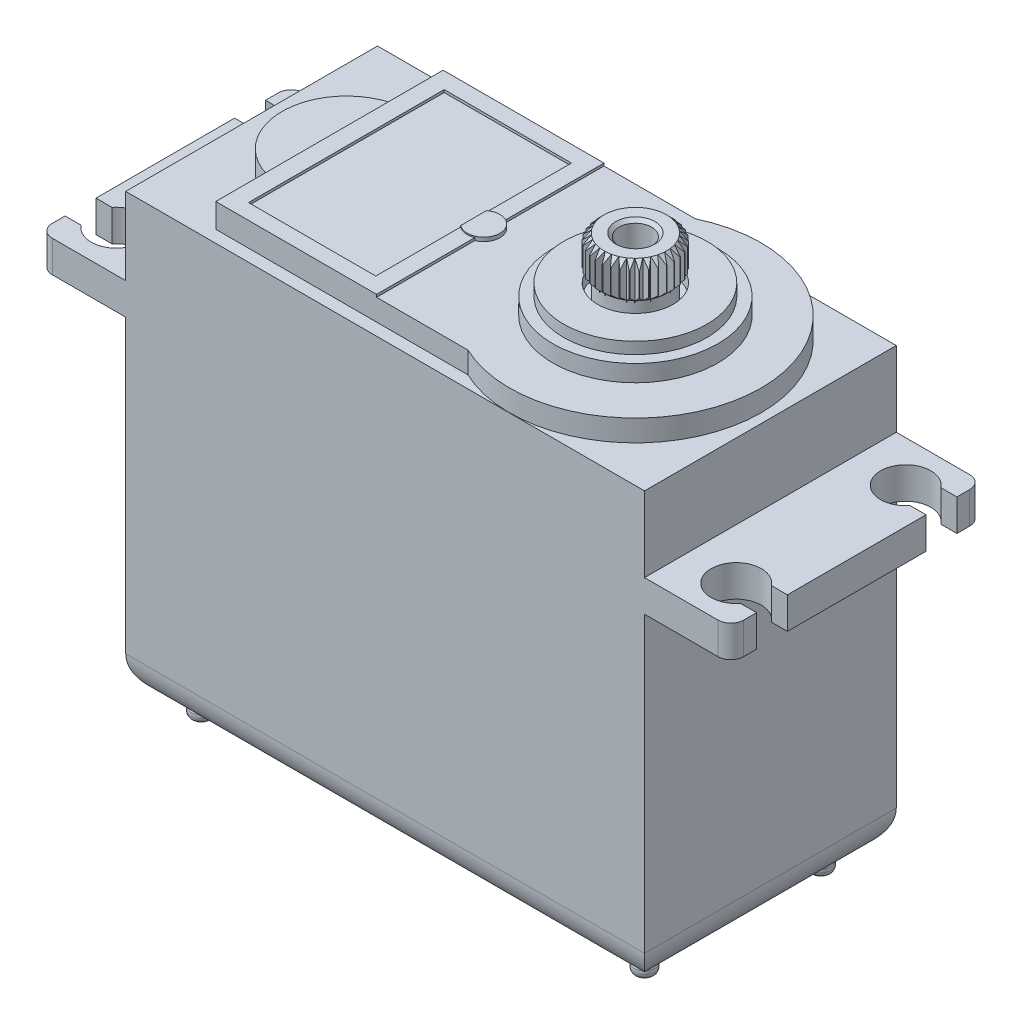
SolidWorks part; units mm, degrees
ref_plane "Front Plane" through (0, 0, 0) normal (0, 0, 1) x (1, 0, 0)
ref_plane "Top Plane" through (0, 0, 0) normal (0, 1, 0) x (1, 0, 0)
ref_plane "Right Plane" through (0, 0, 0) normal (1, 0, 0) x (0, 0, -1)
sketch "Sketch1" plane through (0, 0, 0) normal (0, 1, 0) x (1, 0, 0)
  line L1 (-18.6567, 11.3793) -> (21.6633, 11.3793)
  line L2 (-18.6567, 11.3793) -> (-18.6567, -8.1907)
  line L3 (-18.6567, -8.1907) -> (21.6633, -8.1907)
  line L4 (21.6633, 11.3793) -> (21.6633, -8.1907)
extrude "Boss-Extrude1" add sketch "Sketch1" along normal blind 35.37
sketch "Sketch2" plane through (21.6633, 0, 0) normal (1, 0, 0) x (0, 0, -1)
  line L0 (-8.1907, 0) -> (-8.1907, 3)
  line L1 (-8.1907, 35.37) -> (-8.1907, 0) construction
  line L2 (-8.1907, 3) -> (-5.1907, 0)
  line L3 (-8.1907, 0) -> (11.3793, 0) construction
  line L4 (-5.1907, 0) -> (-8.1907, 0)
  line L5 (1.5943, 0) -> (1.5943, 35.37) construction
  line L6 (-8.1907, 35.37) -> (11.3793, 35.37) construction
  line L7 (8.3793, 0) -> (11.3793, 0)
  line L8 (11.3793, 3) -> (8.3793, 0)
  line L9 (11.3793, 0) -> (11.3793, 3)
extrude "Cut-Extrude1" cut sketch "Sketch2" against normal up to next
sketch "Sketch3" plane through (0, 0, 8.1907) normal (0, 0, 1) x (1, 0, 0)
  line L0 (21.6633, 0) -> (18.6633, 0)
  line L1 (-18.6567, 0) -> (21.6633, 0) construction
  line L2 (18.6633, 0) -> (21.6633, 3)
  line L3 (21.6633, 35.37) -> (21.6633, 3) construction
  line L4 (21.6633, 3) -> (21.6633, 0)
  line L5 (1.5033, 35.37) -> (1.5033, 0) construction
  line L6 (-18.6567, 35.37) -> (21.6633, 35.37) construction
  line L7 (-18.6567, 3) -> (-18.6567, 0)
  line L8 (-15.6567, 0) -> (-18.6567, 3)
  line L9 (-18.6567, 0) -> (-15.6567, 0)
extrude "Cut-Extrude2" cut sketch "Sketch3" against normal up to next
fillet "Fillet2" radius 3 4 edges at (21.6633, 3, -1.5943) (1.5033, 3, 8.1907) (-18.6567, 3, -1.5943) (1.5033, 3, -11.3793)
sketch "Sketch5" plane through (21.6633, 0, 0) normal (1, 0, 0) x (0, 0, -1)
  line L0 (1.5943, 35.37) -> (1.5943, 29.53) construction
  line L1 (-8.1907, 35.37) -> (11.3793, 35.37) construction
  line L2 (-8.1907, 29.53) -> (1.5943, 29.53)
  line L3 (-8.1907, 35.37) -> (-8.1907, 4.2426) construction
  line L4 (1.5943, 29.53) -> (11.3793, 29.53)
  line L5 (11.3793, 35.37) -> (11.3793, 4.2426) construction
  line L6 (11.3793, 29.53) -> (11.3793, 27.07)
  line L7 (11.3793, 27.07) -> (-8.1907, 27.07)
  line L8 (-8.1907, 27.07) -> (-8.1907, 29.53)
extrude "Boss-Extrude2" add sketch "Sketch5" along normal blind 6.71
sketch "Sketch7" plane through (-18.6567, 0, 0) normal (-1, 0, 0) x (0, 0, 1)
  line L0 (-1.5943, 35.37) -> (-1.5943, 29.3613) construction
  line L1 (-11.3793, 29.3613) -> (-1.5943, 29.3613)
  line L2 (-1.5943, 29.3613) -> (8.1907, 29.3613)
  line L3 (8.1907, 29.3613) -> (8.1907, 26.9013)
  line L4 (8.1907, 26.9013) -> (-11.3793, 26.9013)
  line L5 (-11.3793, 26.9013) -> (-11.3793, 29.3613)
  line L6 (-11.3793, 35.37) -> (8.1907, 35.37) construction
  line L7 (8.1907, 35.37) -> (8.1907, 4.2426) construction
  line L8 (-11.3793, 35.37) -> (-11.3793, 4.2426) construction
extrude "Boss-Extrude3" add sketch "Sketch7" along normal blind 6.71
sketch "Sketch8" plane through (0, 29.53, 0) normal (0, 1, 0) x (1, 0, 0)
  line L0 (28.3733, 1.5943) -> (-25.3667, 1.5943) construction
  line L2 (-25.3667, -8.1907) -> (-25.3667, 11.3793) construction
  line L4 (28.3733, -3.7925) -> (27.1303, -3.7925)
  line L5 (28.3733, 11.3793) -> (28.3733, -8.1907) construction
  line L6 (28.3733, 8.181) -> (28.3733, 9.381)
  line L7 (28.3733, 9.381) -> (27.1303, 9.381)
  line L8 (28.3733, 8.181) -> (28.3733, 6.981)
  line L9 (28.3733, 6.981) -> (27.1303, 6.981)
  line L10 (28.3733, -4.9925) -> (28.3733, -3.7925)
  line L11 (28.3733, -6.1925) -> (27.1303, -6.1925)
  line L12 (28.3733, -4.9925) -> (28.3733, -6.1925)
  line L13 (1.5033, 11.3793) -> (1.5033, -8.1907) construction
  line L14 (21.6633, 11.3793) -> (-18.6567, 11.3793) construction
  line L15 (-18.6567, -8.1907) -> (21.6633, -8.1907) construction
  line L24 (-25.3667, 6.981) -> (-24.1237, 6.981)
  line L25 (-25.3667, -4.9925) -> (-25.3667, -6.1925)
  line L26 (-25.3667, -6.1925) -> (-24.1237, -6.1925)
  line L27 (-25.3667, -4.9925) -> (-25.3667, -3.7925)
  line L28 (-25.3667, -3.7925) -> (-24.1237, -3.7925)
  line L29 (-25.3667, 8.181) -> (-25.3667, 6.981)
  line L30 (-25.3667, 9.381) -> (-24.1237, 9.381)
  line L31 (-25.3667, 8.181) -> (-25.3667, 9.381)
  arc A0 (27.1303, -3.7925) -> (27.1303, -6.1925) centre (25.5933, -4.9925) ccw
  arc A1 (27.1303, 6.981) -> (27.1303, 9.381) centre (25.5933, 8.181) cw
  arc A4 (-24.1237, 6.981) -> (-24.1237, 9.381) centre (-22.5867, 8.181) ccw
  arc A5 (-24.1237, -3.7925) -> (-24.1237, -6.1925) centre (-22.5867, -4.9925) cw
extrude "Cut-Extrude3" cut sketch "Sketch8" against normal up to next
sketch "Sketch9" plane through (0, 35.37, 0) normal (0, 1, 0) x (1, 0, 0)
  line L0 (6.9933, -8.1907) -> (6.9933, -7.2426) construction
  line L1 (-18.6567, 6.4311) -> (-12.6067, 6.4311) construction
  line L2 (6.9933, 11.3793) -> (6.9933, 10.4311) construction
  line L3 (-18.6567, -3.2426) -> (-12.6067, -3.2426) construction
  line L4 (-18.6567, -8.1907) -> (-18.6567, 11.3793) construction
  line L5 (-18.6567, 1.5943) -> (21.6633, 1.5943) construction
  line L6 (-12.6067, 10.4311) -> (6.9933, 10.4311)
  line L7 (-18.6567, 11.3793) -> (-18.6567, -8.1907) construction
  line L8 (-12.6067, -7.2426) -> (-12.6067, -3.2426)
  line L9 (21.6633, -8.1907) -> (21.6633, 11.3793) construction
  line L10 (-12.6067, 10.4311) -> (-12.6067, 6.4311)
  line L11 (-12.6067, -7.2426) -> (6.9933, -7.2426)
  line L12 (21.6633, 1.5943) -> (20.9438, 1.5943) construction
  line L13 (21.6633, 11.3793) -> (-18.6567, 11.3793) construction
  arc A0 (6.9933, 10.4311) -> (6.9933, -7.2426) centre (11.1697, 1.5943) cw
  arc A1 (-12.6067, 6.4311) -> (-12.6067, -3.2426) centre (-11.2767, 1.5943) ccw
extrude "Boss-Extrude4" add sketch "Sketch9" along normal blind 1.67
sketch "Sketch10" plane through (0, 37.04, 0) normal (0, 1, 0) x (1, 0, 0)
  circle A1 centre (11.1697, 1.5943) radius 6.415
extrude "Boss-Extrude5" add sketch "Sketch10" along normal blind 1.3
sketch "Sketch11" plane through (0, 38.34, 0) normal (0, 1, 0) x (-1, 0, 0)
  circle A2 centre (-11.1697, -1.5943) radius 5.575
extrude "Boss-Extrude6" add sketch "Sketch11" along normal blind 0.9
sketch "Sketch12" plane through (0, 39.24, 0) normal (0, 1, 0) x (1, 0, 0)
  circle A1 centre (11.1697, 1.5943) radius 2.925
extrude "Cut-Extrude4" cut sketch "Sketch12" against normal blind 1
sketch "Sketch13" plane through (0, 38.24, 0) normal (0, 1, 0) x (-1, 0, 0)
  circle A0 centre (-11.1697, -1.5943) radius 2.425
extrude "Boss-Extrude7" add sketch "Sketch13" along normal blind 1.5
sketch "Sketch14" plane through (0, 39.74, 0) normal (0, 1, 0) x (1, 0, 0)
  circle A0 centre (11.1697, 1.5943) radius 2.925
extrude "Boss-Extrude8" add sketch "Sketch14" along normal blind 2.86
sketch "Sketch15" plane through (0, 42.6, 0) normal (0, 1, 0) x (1, 0, 0)
  circle A0 centre (11.1697, 1.5943) radius 1.27
extrude "Cut-Extrude5" cut sketch "Sketch15" against normal blind 7
sketch "Sketch16" plane through (0, 37.04, 0) normal (0, 1, 0) x (1, 0, 0)
  line L0 (-12.6067, -7.2426) -> (6.9933, -7.2426) construction
  line L1 (-12.6067, 10.4311) -> (-0.1067, 10.4311)
  line L2 (-12.6067, 10.4311) -> (-12.6067, -7.2426)
  line L3 (-12.6067, -7.2426) -> (-0.1067, -7.2426)
  line L4 (-0.1067, 10.4311) -> (-0.1067, -7.2426)
  line L5 (-6.3168, 9.1673) -> (-6.3567, 10.4311) construction
  line L6 (-11.2628, 9.1673) -> (-1.3708, 9.1673)
  line L7 (-11.2628, 9.1673) -> (-11.2628, -6.0433)
  line L8 (-11.2628, -6.0433) -> (-1.3708, -6.0433)
  line L9 (-1.3708, 9.1673) -> (-1.3708, 1.562)
  line L10 (-11.2628, 1.562) -> (-12.6067, 1.5943) construction
  line L11 (-1.3708, 1.562) -> (-0.1067, 1.5943) construction
  line L12 (-6.3168, -6.0433) -> (-6.3567, -7.2426) construction
  line L13 (-1.3708, 1.562) -> (-1.3708, -6.0433)
extrude "Boss-Extrude9" add sketch "Sketch16" along normal blind 0.2
sketch "Sketch17" plane through (0, 37.24, 0) normal (0, 1, 0) x (-1, 0, 0)
  line L0 (1.3708, -1.562) -> (1.3708, -2.562)
  line L1 (1.3708, 6.0433) -> (1.3708, -9.1673) construction
  line L2 (1.3708, -1.562) -> (1.3708, -0.562)
  arc A0 (1.3708, -2.562) -> (1.3708, -0.562) centre (0.592, -1.562) cw
extrude "Boss-Extrude10" add sketch "Sketch17" along normal blind 0.1 and the other way blind 0.5
sketch "Sketch19" plane through (0, 42.6, 0) normal (0, 1, 0) x (1, 0, 0)
  line L0 (10.8404, 4.5007) -> (11.3402, 4.5143) construction
  line L1 (11.3402, 4.5143) -> (11.0903, 4.0075)
  line L2 (11.0903, 4.0075) -> (10.8404, 4.5007)
  line L3 (11.0903, 4.5075) -> (11.0903, 4.0075) construction
  line L4 (10.8404, 4.5007) -> (10.7613, 4.6463)
  line L5 (11.3402, 4.5143) -> (11.4053, 4.6463)
  line L6 (10.7613, 4.6463) -> (11.4053, 4.6463)
  circle A3 centre (11.1697, 1.5943) radius 2.925 construction
  circle A4 centre (11.1697, 1.5943) radius 2.925 construction
extrude "Cut-Extrude11" cut sketch "Sketch19" against normal blind 3
sketch "Sketch21" plane through (0, 0, 0) normal (0, -1, 0) x (1, 0, 0)
  line L0 (1.5033, 5.1907) -> (1.5033, -8.3793) construction
  line L1 (20.7846, 7.3121) -> (17.7846, 7.3121)
  line L2 (20.7846, 7.3121) -> (20.7846, 4.3121)
  line L3 (20.7846, 4.3121) -> (17.7846, 4.3121)
  line L4 (17.7846, 7.3121) -> (17.7846, 4.3121)
  line L5 (-15.6567, 5.1907) -> (18.6633, 5.1907) construction
  line L6 (-15.6567, -8.3793) -> (18.6633, -8.3793) construction
  line L7 (-15.6567, -1.5943) -> (18.6633, -1.5943) construction
  line L8 (-15.6567, -8.3793) -> (-15.6567, 5.1907) construction
  line L9 (18.6633, -8.3793) -> (18.6633, 5.1907) construction
  line L10 (17.7846, -10.5006) -> (17.7846, -7.5006)
  line L11 (20.7846, -7.5006) -> (17.7846, -7.5006)
  line L12 (20.7846, -10.5006) -> (20.7846, -7.5006)
  line L13 (20.7846, -10.5006) -> (17.7846, -10.5006)
  line L14 (-17.778, -7.5006) -> (-14.778, -7.5006)
  line L15 (-14.778, -10.5006) -> (-14.778, -7.5006)
  line L16 (-14.778, 7.3121) -> (-14.778, 4.3121)
  line L17 (-17.778, 4.3121) -> (-14.778, 4.3121)
  line L18 (-17.778, -10.5006) -> (-14.778, -10.5006)
  line L19 (-17.778, -10.5006) -> (-17.778, -7.5006)
  line L20 (-17.778, 7.3121) -> (-17.778, 4.3121)
  line L21 (-17.778, 7.3121) -> (-14.778, 7.3121)
extrude "Cut-Extrude12" cut sketch "Sketch21" against normal blind 1
fillet "Fillet4" radius 1 4 edges at (-14.778, 0.5, -7.5006) (-14.778, 0.5, 4.3121) (17.7846, 0.5, -7.5006) (17.7846, 0.5, 4.3121)
fillet "Fillet5" radius 1 4 edges at (-25.3667, 28.1313, 8.1907) (-25.3667, 28.1313, -11.3793) (28.3733, 28.3, -11.3793) (28.3733, 28.3, 8.1907)
chamfer "Chamfer2" distance 0.5 angle 45 2 edges at (11.2493, 42.6, 1.3297) (11.2493, 39.74, 1.3297)
chamfer "Chamfer3" distance 0.25 angle 45 1 edges at (11.1697, 42.6, -0.3243)
pattern_circular "CirPattern12" count 34 over 360 about axis through (11.1697, 42.6, -1.5943) along (0, -1, 0) of "Cut-Extrude11"
sketch "Sketch23" plane through (0, 1, 0) normal (0, -1, 0) x (1, 0, 0)
  line L0 (1.5033, 5.1907) -> (1.5033, -8.3793) construction
  line L1 (-14.7854, 5.1907) -> (17.792, 5.1907) construction
  line L2 (-14.7854, -8.3793) -> (17.792, -8.3793) construction
  line L3 (18.6633, -1.5943) -> (-15.6567, -1.5943) construction
  line L4 (18.6633, -7.508) -> (18.6633, 4.3195) construction
  line L5 (-15.6567, -7.508) -> (-15.6567, 4.3195) construction
  circle A0 centre (18.7344, -8.4503) radius 0.4237
  circle A1 centre (18.7344, 5.2618) radius 0.4237
  circle A2 centre (-15.7278, 5.2618) radius 0.4237
  circle A3 centre (-15.7278, -8.4503) radius 0.4237
extrude "Boss-Extrude12" add sketch "Sketch23" along normal blind 0.1
sketch "Sketch24" plane through (0, 0.9, 0) normal (0, -1, 0) x (1, 0, 0)
  line L0 (1.5033, 5.1907) -> (1.5033, -8.3793) construction
  line L1 (-14.7854, 5.1907) -> (17.792, 5.1907) construction
  line L2 (-14.7854, -8.3793) -> (17.792, -8.3793) construction
  line L3 (18.6633, -1.5943) -> (-15.6567, -1.5943) construction
  line L4 (18.6633, -7.508) -> (18.6633, 4.3195) construction
  line L5 (-15.6567, -7.508) -> (-15.6567, 4.3195) construction
  circle A0 centre (18.7344, -8.4503) radius 0.8
  circle A1 centre (18.7344, 5.2618) radius 0.8
  circle A2 centre (-15.7278, 5.2618) radius 0.8
  circle A3 centre (-15.7278, -8.4503) radius 0.8
extrude "Boss-Extrude13" add sketch "Sketch24" along normal blind 0.9
fillet "Fillet8" radius 0.45 4 edges at (18.7344, 0, -9.2503) (-15.7278, 0, -7.6503) (-15.7278, 0, 4.4618) (18.7344, 0, 6.0618)
fillet "Fillet9" radius 0.2 4 edges at (-15.7278, 0.9, -7.6503) (-15.7278, 0.9, 4.4618) (18.7344, 0.9, 6.0618) (18.7344, 0.9, -9.2503)
sketch "Sketch25" plane through (0, 0, 0) normal (0, -1, 0) x (1, 0, 0)
  line L0 (18.0844, 5.3868) -> (18.0844, 5.1368)
  line L1 (18.6094, 4.6118) -> (18.8594, 4.6118)
  line L2 (18.0844, 5.3868) -> (18.6094, 5.3868)
  line L3 (18.6094, 5.3868) -> (18.6094, 5.9118)
  line L4 (19.3844, 5.1368) -> (19.3844, 5.3868)
  line L5 (18.8594, 5.9118) -> (18.6094, 5.9118)
  line L6 (1.5033, 5.1907) -> (1.5033, -8.3793) construction
  line L7 (-14.7854, 5.1907) -> (17.792, 5.1907) construction
  line L8 (-14.7854, -8.3793) -> (17.792, -8.3793) construction
  line L9 (18.6633, -1.5943) -> (-15.6567, -1.5943) construction
  line L10 (18.6633, -7.508) -> (18.6633, 4.3195) construction
  line L11 (-15.6567, -7.508) -> (-15.6567, 4.3195) construction
  line L12 (18.6094, -8.3253) -> (18.0844, -8.3253)
  line L13 (18.6094, -7.8003) -> (18.6094, -8.3253)
  line L14 (18.8594, -8.3253) -> (18.8594, -7.8003)
  line L15 (19.3844, -8.3253) -> (18.8594, -8.3253)
  line L16 (18.8594, -8.5753) -> (19.3844, -8.5753)
  line L17 (18.8594, 5.9118) -> (18.8594, 5.3868)
  line L18 (18.8594, 5.3868) -> (19.3844, 5.3868)
  line L19 (18.8594, -9.1003) -> (18.8594, -8.5753)
  line L20 (19.3844, 5.1368) -> (18.8594, 5.1368)
  line L21 (18.8594, 5.1368) -> (18.8594, 4.6118)
  line L22 (18.8594, -9.1003) -> (18.6094, -9.1003)
  line L23 (18.6094, 4.6118) -> (18.6094, 5.1368)
  line L24 (18.6094, 5.1368) -> (18.0844, 5.1368)
  line L25 (19.3844, -8.3253) -> (19.3844, -8.5753)
  line L26 (18.6094, -8.5753) -> (18.6094, -9.1003)
  line L27 (18.0844, -8.5753) -> (18.6094, -8.5753)
  line L28 (18.6094, -7.8003) -> (18.8594, -7.8003)
  line L29 (18.0844, -8.5753) -> (18.0844, -8.3253)
  line L30 (-15.0778, -8.5753) -> (-15.0778, -8.3253)
  line L31 (-15.6028, -7.8003) -> (-15.8528, -7.8003)
  line L32 (-15.0778, -8.5753) -> (-15.6028, -8.5753)
  line L33 (-15.6028, -8.5753) -> (-15.6028, -9.1003)
  line L34 (-16.3778, -8.3253) -> (-16.3778, -8.5753)
  line L35 (-15.6028, 5.1368) -> (-15.0778, 5.1368)
  line L36 (-15.6028, 4.6118) -> (-15.6028, 5.1368)
  line L37 (-15.8528, -9.1003) -> (-15.6028, -9.1003)
  line L38 (-15.8528, 5.1368) -> (-15.8528, 4.6118)
  line L39 (-16.3778, 5.1368) -> (-15.8528, 5.1368)
  line L40 (-15.8528, -9.1003) -> (-15.8528, -8.5753)
  line L41 (-15.8528, 5.3868) -> (-16.3778, 5.3868)
  line L42 (-15.8528, 5.9118) -> (-15.8528, 5.3868)
  line L43 (-15.8528, -8.5753) -> (-16.3778, -8.5753)
  line L44 (-16.3778, -8.3253) -> (-15.8528, -8.3253)
  line L45 (-15.8528, -8.3253) -> (-15.8528, -7.8003)
  line L46 (-15.6028, -7.8003) -> (-15.6028, -8.3253)
  line L47 (-15.6028, -8.3253) -> (-15.0778, -8.3253)
  line L48 (-15.8528, 5.9118) -> (-15.6028, 5.9118)
  line L49 (-16.3778, 5.1368) -> (-16.3778, 5.3868)
  line L50 (-15.6028, 5.3868) -> (-15.6028, 5.9118)
  line L51 (-15.0778, 5.3868) -> (-15.6028, 5.3868)
  line L52 (-15.6028, 4.6118) -> (-15.8528, 4.6118)
  line L53 (-15.0778, 5.3868) -> (-15.0778, 5.1368)
extrude "Cut-Extrude14" cut sketch "Sketch25" against normal blind 0.6
move or copy body "Body-Move/Copy1" [suppressed] bodies to move or copy 132
